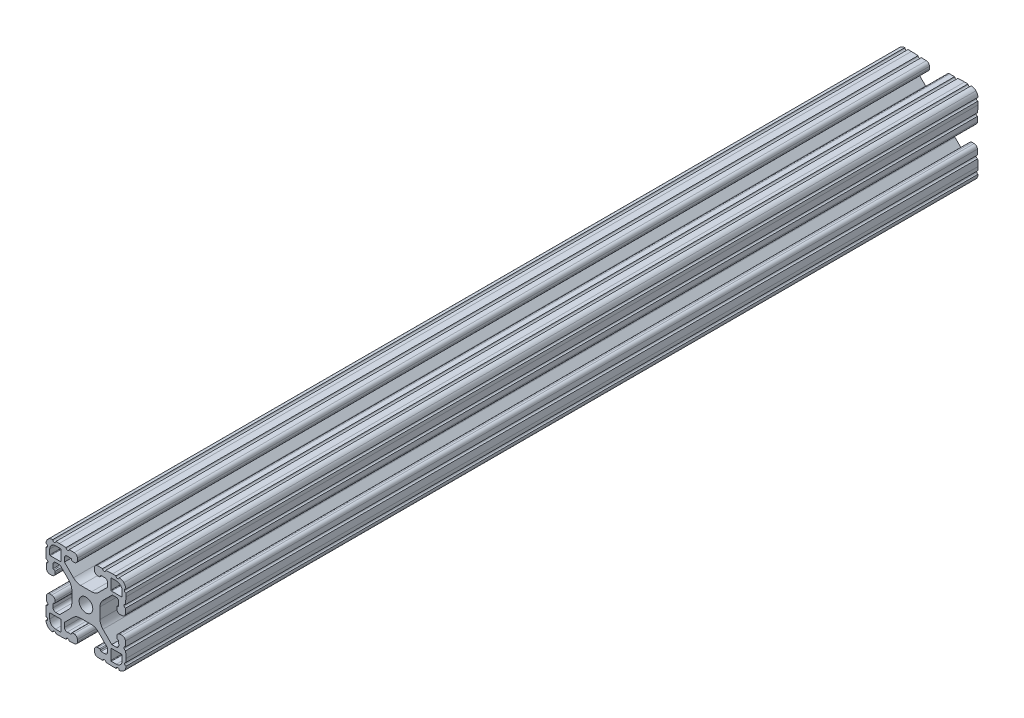
SolidWorks part; units mm, degrees
material "6061-T6 (SS)"
ref_plane "Front Plane" through (0, 0, 0) normal (0, 0, 1) x (1, 0, 0)
ref_plane "Top Plane" through (0, 0, 0) normal (0, 1, 0) x (1, 0, 0)
ref_plane "Right Plane" through (0, 0, 0) normal (1, 0, 0) x (0, 0, -1)
ref_plane "Plane1" through (0, 0, -25.4) normal (0, 0, -1) x (-1, 0, 0)
sketch "Sketch1" plane through (0, 0, -25.4) normal (0, 0, -1) x (-1, 0, 0)
  line L0 (-83.3577, 88.2941) -> (-83.3577, 93.1709)
  line L1 (-83.1037, 93.4249) -> (-80.767, 93.4249)
  line L2 (-77.9729, 90.6309) -> (-77.9729, 88.2941)
  line L3 (-78.2269, 88.0401) -> (-83.1037, 88.0401)
  line L4 (-83.3577, 59.2291) -> (-83.3577, 64.1059)
  line L5 (-83.1037, 64.3599) -> (-78.2269, 64.3599)
  line L6 (-77.9729, 64.1059) -> (-77.9729, 61.7691)
  line L7 (-80.767, 58.9751) -> (-83.1037, 58.9751)
  line L8 (-107.1423, 93.1709) -> (-107.1423, 88.2941)
  line L9 (-107.3963, 88.0401) -> (-112.2731, 88.0401)
  line L10 (-112.5271, 88.2941) -> (-112.5271, 90.6309)
  line L11 (-109.733, 93.4249) -> (-107.3963, 93.4249)
  line L12 (-107.1423, 64.1059) -> (-107.1423, 59.2291)
  line L13 (-107.3963, 58.9751) -> (-109.733, 58.9751)
  line L14 (-112.5271, 61.7691) -> (-112.5271, 64.1059)
  line L15 (-112.2731, 64.3599) -> (-107.3963, 64.3599)
  line L16 (-88.0437, 91.8626) -> (-86.2967, 91.9236)
  line L17 (-84.9824, 90.6544) -> (-84.9824, 88.8002)
  line L18 (-84.9824, 88.8002) -> (-89.3066, 84.476)
  line L19 (-92.7196, 83.0295) -> (-97.9616, 83.0295)
  line L20 (-101.3202, 84.4207) -> (-105.516, 88.6165)
  line L21 (-105.516, 88.6165) -> (-105.516, 90.7313)
  line L22 (-104.2017, 92.0006) -> (-102.4547, 91.9396)
  line L23 (-101.7262, 91.1059) -> (-100.9297, 91.0781)
  line L24 (-99.2999, 92.6519) -> (-99.2999, 93.5668)
  line L25 (-100.8197, 95.1407) -> (-103.2119, 95.2242)
  line L26 (-104.735, 95.2774) -> (-107.9359, 95.3892)
  line L27 (-107.9359, 95.3892) -> (-109.5615, 95.3892)
  line L28 (-114.2859, 90.6648) -> (-114.2859, 89.0392)
  line L29 (-114.2859, 89.0392) -> (-114.1741, 85.8383)
  line L30 (-114.1209, 84.3152) -> (-114.0374, 81.9231)
  line L31 (-112.4635, 80.4032) -> (-111.5486, 80.4032)
  line L32 (-109.9748, 82.033) -> (-110.0026, 82.8295)
  line L33 (-110.8377, 83.5577) -> (-110.8987, 85.3047)
  line L34 (-109.6294, 86.619) -> (-107.8072, 86.619)
  line L35 (-107.8072, 86.619) -> (-103.3649, 82.1768)
  line L36 (-101.9737, 78.8182) -> (-101.9737, 73.576)
  line L37 (-103.3649, 70.2174) -> (-107.5607, 66.0217)
  line L38 (-107.5607, 66.0217) -> (-109.6524, 66.0217)
  line L39 (-110.9217, 67.336) -> (-110.8607, 69.083)
  line L40 (-110.0322, 69.8124) -> (-110.0043, 70.6089)
  line L41 (-111.5782, 72.2387) -> (-112.4931, 72.2387)
  line L42 (-114.0669, 70.7189) -> (-114.1505, 68.3267)
  line L43 (-114.2036, 66.8036) -> (-114.3154, 63.6027)
  line L44 (-114.3154, 63.6027) -> (-114.3154, 61.9626)
  line L45 (-109.6111, 57.1437) -> (-107.9855, 57.1437)
  line L46 (-107.9855, 57.1437) -> (-104.7846, 57.2555)
  line L47 (-103.2615, 57.3086) -> (-100.8694, 57.3922)
  line L48 (-99.3495, 58.966) -> (-99.3495, 59.8809)
  line L49 (-100.9794, 61.4548) -> (-101.7758, 61.4269)
  line L50 (-102.5054, 60.599) -> (-104.2524, 60.538)
  line L51 (-105.5667, 61.8072) -> (-105.5667, 63.6295)
  line L52 (-105.5667, 63.6295) -> (-101.1311, 68.065)
  line L53 (-97.7725, 69.4562) -> (-92.5304, 69.4562)
  line L54 (-89.1717, 68.065) -> (-84.976, 63.8692)
  line L55 (-84.976, 63.8692) -> (-84.976, 61.7811)
  line L56 (-86.2903, 60.5118) -> (-88.0373, 60.5728)
  line L57 (-88.7596, 61.4332) -> (-89.5561, 61.461)
  line L58 (-91.1859, 59.8872) -> (-91.1859, 58.9723)
  line L59 (-89.6661, 57.3985) -> (-87.2739, 57.3149)
  line L60 (-85.7508, 57.2617) -> (-82.5499, 57.15)
  line L61 (-82.5499, 57.15) -> (-80.9244, 57.15)
  line L62 (-76.2, 61.8744) -> (-76.2, 63.4999)
  line L63 (-76.2, 63.4999) -> (-76.3117, 66.7008)
  line L64 (-76.3649, 68.2239) -> (-76.4484, 70.6161)
  line L65 (-78.0223, 72.1359) -> (-78.9372, 72.1359)
  line L66 (-80.511, 70.5061) -> (-80.4832, 69.7096)
  line L67 (-79.6552, 68.9801) -> (-79.5942, 67.2331)
  line L68 (-80.8634, 65.9188) -> (-82.6857, 65.9188)
  line L69 (-82.6857, 65.9188) -> (-87.1213, 70.3543)
  line L70 (-88.5125, 73.7128) -> (-88.5126, 78.955)
  line L71 (-87.1214, 82.3137) -> (-82.9257, 86.5095)
  line L72 (-82.9257, 86.5095) -> (-80.8375, 86.5095)
  line L73 (-79.5682, 85.1951) -> (-79.6293, 83.4482)
  line L74 (-80.4896, 82.7258) -> (-80.5175, 81.9294)
  line L75 (-78.9436, 80.2995) -> (-78.0287, 80.2995)
  line L76 (-76.4549, 81.8194) -> (-76.3713, 84.2115)
  line L77 (-76.3182, 85.7346) -> (-76.2064, 88.9355)
  line L78 (-76.2064, 88.9355) -> (-76.2064, 90.5611)
  line L79 (-80.9308, 95.2855) -> (-82.5564, 95.2855)
  line L80 (-82.5564, 95.2855) -> (-85.7573, 95.1737)
  line L81 (-87.2803, 95.1205) -> (-89.6725, 95.037)
  line L82 (-91.1924, 93.4632) -> (-91.1924, 92.5483)
  line L83 (-89.5625, 90.9744) -> (-88.7661, 91.0023)
  arc A0 (-83.3577, 93.1709) -> (-83.1037, 93.4249) centre (-83.1037, 93.1709) cw
  arc A1 (-80.767, 93.4249) -> (-77.9729, 90.6309) centre (-80.7669, 90.6309) cw
  arc A2 (-77.9729, 88.2941) -> (-78.2269, 88.0401) centre (-78.2269, 88.2941) cw
  arc A3 (-83.1037, 88.0401) -> (-83.3577, 88.2941) centre (-83.1037, 88.2941) cw
  arc A4 (-83.1037, 58.9751) -> (-83.3577, 59.2291) centre (-83.1037, 59.2291) cw
  arc A5 (-83.3577, 64.1059) -> (-83.1037, 64.3599) centre (-83.1037, 64.1059) cw
  arc A6 (-78.2269, 64.3599) -> (-77.9729, 64.1059) centre (-78.2269, 64.1059) cw
  arc A7 (-77.9729, 61.7691) -> (-80.767, 58.9751) centre (-80.7669, 61.7691) cw
  arc A8 (-107.3963, 93.4249) -> (-107.1423, 93.1709) centre (-107.3963, 93.1709) cw
  arc A9 (-107.1423, 88.2941) -> (-107.3963, 88.0401) centre (-107.3963, 88.2941) cw
  arc A10 (-112.2731, 88.0401) -> (-112.5271, 88.2941) centre (-112.2731, 88.2941) cw
  arc A11 (-112.5271, 90.6309) -> (-109.733, 93.4249) centre (-109.7331, 90.6309) cw
  arc A12 (-107.1423, 59.2291) -> (-107.3963, 58.9751) centre (-107.3963, 59.2291) cw
  arc A13 (-109.733, 58.9751) -> (-112.5271, 61.7691) centre (-109.7331, 61.7691) cw
  arc A14 (-112.5271, 64.1059) -> (-112.2731, 64.3599) centre (-112.2731, 64.1059) cw
  arc A15 (-107.3963, 64.3599) -> (-107.1423, 64.1059) centre (-107.3963, 64.1059) cw
  circle A16 centre (-95.25, 76.2) radius 3.2639
  arc A17 (-88.7661, 91.0023) -> (-88.3984, 91.383) centre (-88.7794, 91.383) ccw
  arc A18 (-88.3984, 91.383) -> (-88.0437, 91.8626) centre (-88.0304, 91.4819) cw
  arc A19 (-86.2967, 91.9236) -> (-84.9824, 90.6544) centre (-86.2524, 90.6544) cw
  arc A20 (-89.3066, 84.476) -> (-92.7196, 83.0295) centre (-92.7196, 87.7793) cw
  arc A21 (-97.9616, 83.0295) -> (-101.3202, 84.4207) centre (-97.9616, 87.7793) cw
  arc A22 (-105.516, 90.7313) -> (-104.2017, 92.0006) centre (-104.246, 90.7313) cw
  arc A23 (-102.4547, 91.9396) -> (-102.087, 91.5588) centre (-102.468, 91.5588) cw
  arc A24 (-102.087, 91.5588) -> (-101.7262, 91.1059) centre (-101.7129, 91.4867) ccw
  arc A25 (-100.9297, 91.0781) -> (-99.2999, 92.6519) centre (-100.8747, 92.6519) ccw
  arc A26 (-99.2999, 93.5668) -> (-100.8197, 95.1407) centre (-100.8747, 93.5668) ccw
  arc A27 (-103.2119, 95.2242) -> (-104.735, 95.2774) centre (-103.9735, 95.2508) cw
  arc A28 (-109.5615, 95.3892) -> (-111.0855, 95.3892) centre (-110.3235, 95.3892) cw
  arc A29 (-111.0855, 95.3892) -> (-113.3432, 94.4465) centre (-111.0855, 92.2142) ccw
  arc A30 (-113.3432, 94.4465) -> (-114.2859, 92.1888) centre (-111.1109, 92.1888) ccw
  arc A31 (-114.2859, 92.1888) -> (-114.2859, 90.6648) centre (-114.2859, 91.4268) cw
  arc A32 (-114.1741, 85.8383) -> (-114.1209, 84.3152) centre (-114.1475, 85.0768) cw
  arc A33 (-114.0374, 81.9231) -> (-112.4635, 80.4032) centre (-112.4635, 81.978) ccw
  arc A34 (-111.5486, 80.4032) -> (-109.9748, 82.033) centre (-111.5486, 81.978) ccw
  arc A35 (-110.0026, 82.8295) -> (-110.3834, 83.1972) centre (-110.3834, 82.8162) ccw
  arc A36 (-110.3834, 83.1972) -> (-110.8377, 83.5577) centre (-110.4569, 83.571) cw
  arc A37 (-110.8987, 85.3047) -> (-109.6294, 86.619) centre (-109.6294, 85.349) cw
  arc A38 (-103.3649, 82.1768) -> (-101.9737, 78.8182) centre (-106.7235, 78.8182) cw
  arc A39 (-101.9737, 73.576) -> (-103.3649, 70.2174) centre (-106.7235, 73.576) cw
  arc A40 (-109.6524, 66.0217) -> (-110.9217, 67.336) centre (-109.6524, 67.2917) cw
  arc A41 (-110.8607, 69.083) -> (-110.4799, 69.4507) centre (-110.4799, 69.0697) cw
  arc A42 (-110.4799, 69.4507) -> (-110.0322, 69.8124) centre (-110.413, 69.8257) ccw
  arc A43 (-110.0043, 70.6089) -> (-111.5782, 72.2387) centre (-111.5782, 70.6639) ccw
  arc A44 (-112.4931, 72.2387) -> (-114.0669, 70.7189) centre (-112.4931, 70.6639) ccw
  arc A45 (-114.1505, 68.3267) -> (-114.2036, 66.8036) centre (-114.1771, 67.5652) cw
  arc A46 (-114.3154, 61.9626) -> (-114.3332, 60.4644) centre (-114.4639, 61.2152) cw
  arc A47 (-114.3332, 60.4644) -> (-113.3928, 58.0864) centre (-111.1605, 60.3441) ccw
  arc A48 (-113.3928, 58.0864) -> (-111.1351, 57.1437) centre (-111.1351, 60.3187) ccw
  arc A49 (-111.1351, 57.1437) -> (-109.6111, 57.1437) centre (-110.3731, 57.1437) cw
  arc A50 (-104.7846, 57.2555) -> (-103.2615, 57.3086) centre (-104.0231, 57.2821) cw
  arc A51 (-100.8694, 57.3922) -> (-99.3495, 58.966) centre (-100.9243, 58.966) ccw
  arc A52 (-99.3495, 59.8809) -> (-100.9794, 61.4548) centre (-100.9243, 59.8809) ccw
  arc A53 (-101.7758, 61.4269) -> (-102.1435, 61.0462) centre (-101.7625, 61.0462) ccw
  arc A54 (-102.1435, 61.0462) -> (-102.5054, 60.599) centre (-102.5187, 60.9797) cw
  arc A55 (-104.2524, 60.538) -> (-105.5667, 61.8072) centre (-104.2967, 61.8072) cw
  arc A56 (-101.1311, 68.065) -> (-97.7725, 69.4562) centre (-97.7725, 64.7064) cw
  arc A57 (-92.5304, 69.4562) -> (-89.1717, 68.065) centre (-92.5304, 64.7064) cw
  arc A58 (-84.976, 61.7811) -> (-86.2903, 60.5118) centre (-86.246, 61.7811) cw
  arc A59 (-88.0373, 60.5728) -> (-88.405, 60.9536) centre (-88.024, 60.9536) cw
  arc A60 (-88.405, 60.9536) -> (-88.7596, 61.4332) centre (-88.7729, 61.0524) ccw
  arc A61 (-89.5561, 61.461) -> (-91.1859, 59.8872) centre (-89.6111, 59.8872) ccw
  arc A62 (-91.1859, 58.9723) -> (-89.6661, 57.3985) centre (-89.6111, 58.9723) ccw
  arc A63 (-87.2739, 57.3149) -> (-85.7508, 57.2617) centre (-86.5124, 57.2883) cw
  arc A64 (-80.9244, 57.15) -> (-79.4004, 57.15) centre (-80.1624, 57.15) cw
  arc A65 (-79.4004, 57.15) -> (-77.1426, 58.0927) centre (-79.4004, 60.325) ccw
  arc A66 (-77.1426, 58.0927) -> (-76.2, 60.3504) centre (-79.375, 60.3504) ccw
  arc A67 (-76.2, 60.3504) -> (-76.2, 61.8744) centre (-76.2, 61.1124) cw
  arc A68 (-76.3117, 66.7008) -> (-76.3649, 68.2239) centre (-76.3383, 67.4624) cw
  arc A69 (-76.4484, 70.6161) -> (-78.0223, 72.1359) centre (-78.0223, 70.5611) ccw
  arc A70 (-78.9372, 72.1359) -> (-80.511, 70.5061) centre (-78.9372, 70.5611) ccw
  arc A71 (-80.4832, 69.7096) -> (-80.1024, 69.342) centre (-80.1024, 69.723) ccw
  arc A72 (-80.1024, 69.342) -> (-79.6552, 68.9801) centre (-80.036, 68.9668) cw
  arc A73 (-79.5942, 67.2331) -> (-80.8634, 65.9188) centre (-80.8634, 67.1888) cw
  arc A74 (-87.1213, 70.3543) -> (-88.5125, 73.7128) centre (-83.7627, 73.7129) cw
  arc A75 (-88.5126, 78.955) -> (-87.1214, 82.3137) centre (-83.7628, 78.9551) cw
  arc A76 (-80.8375, 86.5095) -> (-79.5682, 85.1951) centre (-80.8375, 85.2395) cw
  arc A77 (-79.6293, 83.4482) -> (-80.01, 83.0805) centre (-80.01, 83.4615) cw
  arc A78 (-80.01, 83.0805) -> (-80.4896, 82.7258) centre (-80.1089, 82.7125) ccw
  arc A79 (-80.5175, 81.9294) -> (-78.9436, 80.2995) centre (-78.9436, 81.8743) ccw
  arc A80 (-78.0287, 80.2995) -> (-76.4549, 81.8194) centre (-78.0287, 81.8743) ccw
  arc A81 (-76.3713, 84.2115) -> (-76.3182, 85.7346) centre (-76.3448, 84.9731) cw
  arc A82 (-76.2064, 90.5611) -> (-76.2064, 92.0851) centre (-76.2064, 91.3231) cw
  arc A83 (-76.2064, 92.0851) -> (-77.1491, 94.3428) centre (-79.3814, 92.0851) ccw
  arc A84 (-77.1491, 94.3428) -> (-79.4068, 95.2855) centre (-79.4068, 92.1105) ccw
  arc A85 (-79.4068, 95.2855) -> (-80.9308, 95.2855) centre (-80.1688, 95.2855) cw
  arc A86 (-85.7573, 95.1737) -> (-87.2803, 95.1205) centre (-86.5188, 95.1471) cw
  arc A87 (-89.6725, 95.037) -> (-91.1924, 93.4632) centre (-89.6176, 93.4632) ccw
  arc A88 (-91.1924, 92.5483) -> (-89.5625, 90.9744) centre (-89.6176, 92.5483) ccw
extrude "Boss-Extrude1" add sketch "Sketch1" against normal blind 406.4
